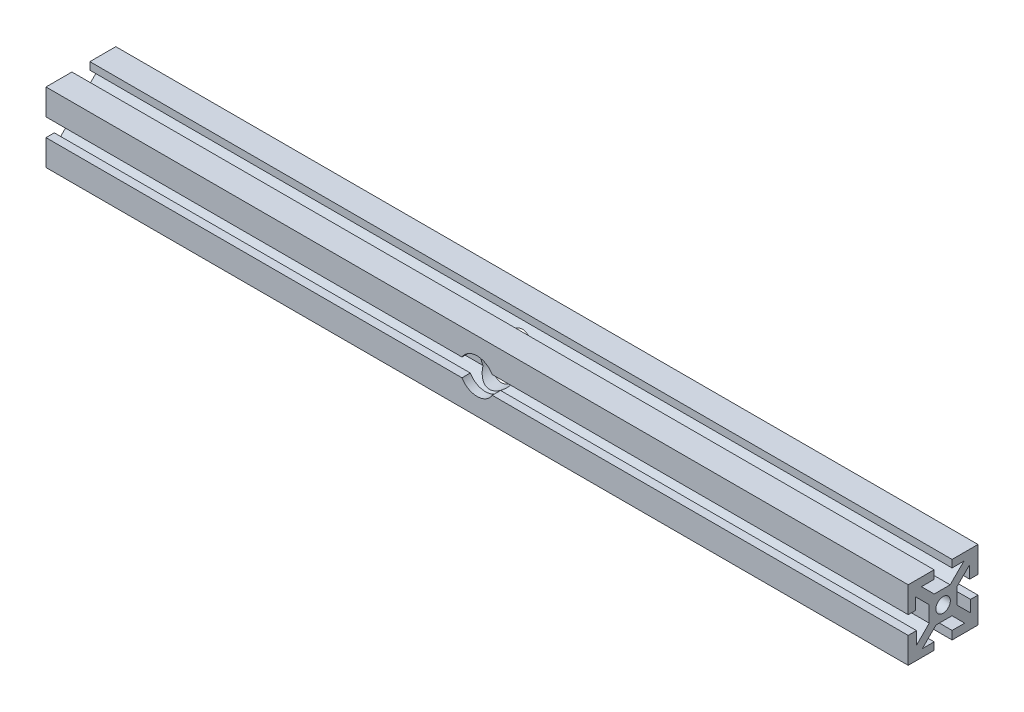
SolidWorks part; units mm, degrees
ref_plane "Front Plane" through (0, 0, 0) normal (0, 0, 1) x (1, 0, 0)
ref_plane "Top Plane" through (0, 0, 0) normal (0, 1, 0) x (1, 0, 0)
ref_plane "Right Plane" through (0, 0, 0) normal (1, 0, 0) x (0, 0, -1)
sketch "Sketch1" plane through (0, 0, 0) normal (1, 0, 0) x (0, 0, -1)
  line L0 (2.5534, 5) -> (7.4749, 9.9215)
  line L1 (-5, 5) -> (5, 5)
  line L2 (-5, 5) -> (-5, -5)
  line L3 (-5, -5) -> (5, -5)
  line L4 (5, 5) -> (5, -5)
  line L5 (-5, 5) -> (5, -5) construction
  line L6 (-5, -5) -> (5, 5) construction
  line L7 (7.4749, 9.9215) -> (9.5962, 7.8001)
  line L8 (9.5962, 7.8001) -> (5, 3.2039)
  line L9 (5, 5) -> (13.6489, 13.6489) construction
  line L10 (7.4749, 9.9215) -> (3.24, 9.9215)
  line L11 (3.24, 9.9215) -> (3.24, 12.5962)
  line L12 (3.24, 12.5962) -> (12.5962, 12.5962)
  line L13 (9.5962, 7.8001) -> (9.5962, 3.24)
  line L14 (9.5962, 3.24) -> (12.5962, 3.24)
  line L15 (12.5962, 3.24) -> (12.5962, 12.5962)
  line L17 (0, 0) -> (0, 24.089) construction
  line L18 (0, 0) -> (23.75, 0) construction
  circle A0 centre (0, 0) radius 2.605
  point P0 (0, 0)
  dimension "D1" = 5.21
  dimension "D2" = 10
  dimension "D3" = 10
  dimension "D4" = 3
  dimension "D5" = 1.27
  dimension "D6" = 6.5
  dimension "D7" = 3.24
  dimension "D8" = 3.24
  dimension "D9" = 3
extrude "Boss-Extrude1" add sketch "Sketch1" along normal blind 311.15 contours L4 L1 L2 L3 A0 | L8 L7 L0 L1 L4 | L14 L15 L12 L11 L10 L7 L13 region at (0, 4.8586, -3.7767) region at (0, 6.7479, -6.3823) region at (0, 9.18, -9.3105)
ref_axis "Axis1" through (0, 0, 0) along (1, 0, 0)
pattern_circular "CirPattern1" count 4 over 360 about axis through (0, 0, 0) along (1, 0, 0) of "Boss-Extrude1"
sketch "Sketch2" plane through (0, 0, 12.5962) normal (0, 0, 1) x (1, 0, 0)
  circle A0 centre (155.575, 0) radius 6.35
  dimension "D1" = 12.7
  dimension "D2" = 155.575
extrude "Cut-Extrude1" cut sketch "Sketch2" against normal blind 30
